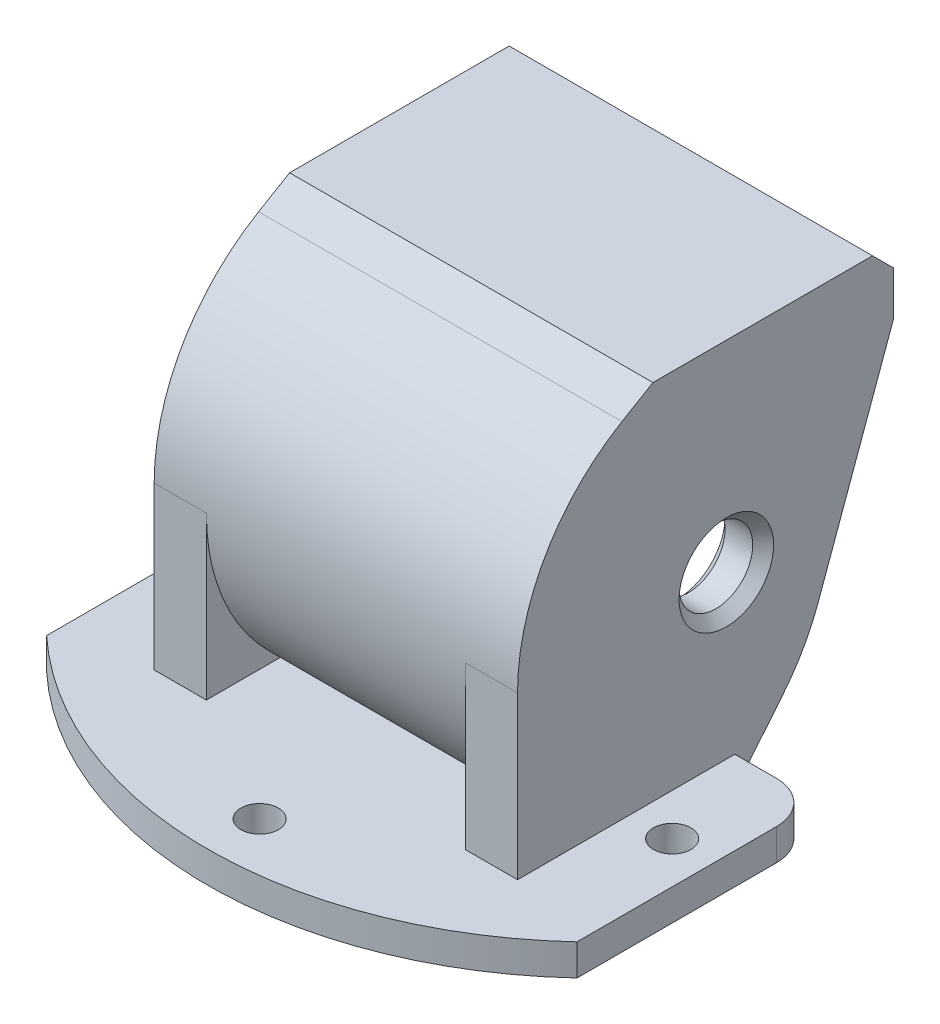
SolidWorks part; units mm, degrees
ref_plane "Front Plane" through (0, 0, 0) normal (0, 0, 1) x (1, 0, 0)
ref_plane "Top Plane" through (0, 0, 0) normal (0, 1, 0) x (1, 0, 0)
ref_plane "Right Plane" through (0, 0, 0) normal (1, 0, 0) x (0, 0, -1)
sketch "Sketch1" plane through (0, 0, 0) normal (1, 0, 0) x (0, 0, -1)
  line L0 (0, 17.5) -> (0, -17.5) construction
  line L1 (0, 17.5) -> (-10, 17.5)
  line L2 (10, 17.5) -> (10, -17.5) construction
  line L3 (0, -17.5) -> (-10, -17.5)
  line L4 (-10, 17.5) -> (-10, -17.5) construction
  line L5 (0, 0) -> (10, 0) construction
  line L6 (0, 0) -> (-10, 0) construction
  line L7 (0, 0) -> (-10, 0) construction
  line L8 (-10, 0) -> (-20, 0) construction
  arc A0 (0, -17.5) -> (0, 17.5) centre (-10.3125, 0) ccw
  arc A1 (-10, 17.5) -> (-10, -17.5) centre (0.3125, 0) ccw
  dimension "D3" = 20
  dimension "D1" = 35
extrude "Boss-Extrude1" add sketch "Sketch1" against normal mid plane 34.8
sketch "Sketch2" plane through (0, 0, 0) normal (1, 0, 0) x (0, 0, -1)
  line L0 (0, 17.5) -> (-10, 17.5) construction
  line L1 (-10, -17.5) -> (0, -17.5) construction
  line L2 (-16, 0) -> (-20, 0) construction
  line L4 (-10, -17.5) -> (0, -17.5)
  line L5 (0, 17.5) -> (-10, 17.5)
  line L6 (-6, -17.5) -> (0, -17.5)
  line L7 (0, 17.5) -> (-6, 17.5)
  arc A0 (-6, 17.5) -> (-6, -17.5) centre (4.3125, 0) ccw
  arc A1 (-10, 17.5) -> (-10, -17.5) centre (0.3125, 0) ccw construction
  arc A4 (-10, 17.5) -> (-10, -17.5) centre (0.3125, 0) ccw
  arc A5 (0, -17.5) -> (0, 17.5) centre (-10.3125, 0) ccw
  arc A7 (0, -17.5) -> (0, 17.5) centre (-10.3125, 0) ccw
  dimension "D1" = 0
  dimension "D2" = 4
extrude "Cut-Extrude1" cut sketch "Sketch2" along normal mid plane 25.5
sketch "Sketch3" plane through (0, 0, 0) normal (1, 0, 0) x (0, 0, -1)
  line L0 (-9.5, -17.5) -> (-9.5, -24)
  line L1 (-10, -17.5) -> (0, -17.5) construction
  line L2 (-0.5, -24) -> (-0.5, -17.5)
  line L3 (-0.5, -17.5) -> (-9.5, -17.5)
  line L4 (-5, -28.5) -> (-5, -17.5) construction
  arc A0 (-9.5, -24) -> (-0.5, -24) centre (-5, -24) ccw
  dimension "D1" = 9
  dimension "D2" = 6.5
extrude "Boss-Extrude2" add sketch "Sketch3" along normal mid plane 10
sketch "Sketch4" plane through (17.4, 0, 0) normal (1, 0, 0) x (0, 0, -1)
  line L0 (-13.4374, -9.8761) -> (0.9816, -18.201)
  line L1 (0.8089, -18.5) -> (-8.303, -18.5)
  line L4 (-13.4374, -9.8761) -> (-17.4374, -9.8761)
  line L5 (0.8089, -18.5) -> (0.9816, -18.201)
  line L8 (0, 0) -> (14.9634, 0.0217) construction
  line L9 (14.9634, 0.0217) -> (14.9855, -15.25) construction
  line L10 (69.9999, 0.1014) -> (0, 0) construction
  line L12 (-10, -17.5) -> (-8.303, -18.5)
  line L13 (0.9816, -18.201) -> (8.6174, -4.9753) construction
  line L14 (0, 0) -> (8.6174, -4.9753) construction
  line L15 (0, 0) -> (-8.348, 0) construction
  line L16 (-10, -17.5) -> (0, -17.5) construction
  arc A0 (-10, 17.5) -> (-10, -17.5) centre (0.3125, 0) ccw construction
  arc A2 (-6, 17.5) -> (-6, -17.5) centre (4.3125, 0) ccw construction
  arc A3 (-6, 17.5) -> (-6, -17.5) centre (4.3125, 0) ccw construction
  arc A4 (-17.4374, -9.8761) -> (-10, -17.5) centre (0.3125, 0) ccw
  dimension "D1" = 30
  dimension "D2" = 0.299
  dimension "D3" = 1
extrude "Boss-Extrude3" add sketch "Sketch4" against normal up to surface (34.8 mm away) up to face at (-17.4, 0, 5)
sketch "Sketch5" plane through (17.4, 0, 0) normal (1, 0, 0) x (0, 0, -1)
  line L4 (-8.303, -18.5) -> (0.8089, -18.5) construction
  line L5 (5.426, -12.8412) -> (0.8089, -18.5)
  line L6 (0.8089, -18.5) -> (0.9816, -18.201) construction
  line L7 (0.8089, -18.5) -> (-1.1911, -18.5)
  line L8 (-1.1911, -18.5) -> (-1.1911, -17.5)
  line L9 (-1.1911, -17.5) -> (5.426, -12.8412)
  arc A3 (0, -17.5) -> (0, 17.5) centre (-10.3125, 0) ccw construction
  dimension "D1" = 1
  dimension "D2" = 2
extrude "Boss-Extrude4" add sketch "Sketch5" against normal up to surface (4.65 mm away) up to face at (12.75, -1.6725, 3.0481)
sketch "Sketch6" plane through (-17.4, 0, 0) normal (-1, 0, 0) x (0, 0, 1)
  line L2 (-5.426, -12.8412) -> (-0.8089, -18.5)
  line L3 (-5.426, -12.8412) -> (-0.8089, -18.5)
  line L4 (-0.8089, -18.5) -> (1.1911, -18.5)
  line L5 (-0.8089, -18.5) -> (1.1911, -18.5)
  line L12 (1.1911, -18.5) -> (1.1911, -17.5)
  line L13 (1.1911, -18.5) -> (1.1911, -17.5)
  line L14 (1.1911, -17.5) -> (-5.426, -12.8412)
  line L15 (1.1911, -17.5) -> (-5.426, -12.8412)
  dimension "D1" = 0
extrude "Boss-Extrude5" add sketch "Sketch6" against normal up to surface (4.65 mm away) up to face at (-12.75, -1.6725, 3.0481)
sketch "Sketch7" plane through (17.4, 0, 0) normal (1, 0, 0) x (0, 0, -1)
  line L0 (-10, 17.5) -> (-7.0303, 19.25)
  line L1 (-7.0303, 19.25) -> (16, 19.25)
  line L2 (16, 19.25) -> (16, 12.9763)
  line L3 (0, 0) -> (2.3856, 15.0622) construction
  line L4 (3.1052, 15.25) -> (-13.1052, 15.25)
  line L6 (0, 0) -> (0, 15.25) construction
  line L7 (69.1382, -10.9504) -> (0, 0) construction
  line L8 (86.7145, 1.7059) -> (32.5901, 10.2783) construction
  line L9 (0, 17.5) -> (-10, 17.5) construction
  line L10 (3.1052, 15.25) -> (16, 12.9763)
  line L11 (0, 17.5) -> (-10, 17.5) construction
  line L13 (10, 0) -> (10, 11.0966) construction
  line L14 (0, 0) -> (69.1382, 0) construction
  arc A0 (-10, 17.5) -> (-10, -17.5) centre (0.3125, 0) ccw construction
  arc A1 (-10, 17.5) -> (-13.1052, 15.25) centre (0.3125, 0) ccw
  arc A3 (5.426, -12.8412) -> (0, 17.5) centre (-10.3125, 0) ccw construction
  dimension "D1" = 10
  dimension "D2" = 4
  dimension "D3" = 6
extrude "Boss-Extrude6" add sketch "Sketch7" against normal up to surface (34.8 mm away) up to face at (-17.4, -5.1825, 4.1831)
sketch "Sketch8" plane through (17.4, 0, 0) normal (1, 0, 0) x (0, 0, -1)
  line L0 (16, 12.9763) -> (8.7832, -6.9248)
  line L2 (3.1052, 15.25) -> (16, 12.9763)
  arc A0 (5.426, -12.8412) -> (3.1052, 15.25) centre (-10.3125, 0) ccw construction
  arc A1 (8.7832, -6.9248) -> (3.1052, 15.25) centre (-10.3125, 0) ccw
extrude "Boss-Extrude7" add sketch "Sketch8" against normal up to surface (4.65 mm away) up to face at (12.75, -4.6143, 1.8315)
sketch "Sketch9" plane through (-17.4, 0, 0) normal (-1, 0, 0) x (0, 0, 1)
  line L2 (-16, 12.9763) -> (-8.7832, -6.9248)
  line L3 (-3.1052, 15.25) -> (-16, 12.9763)
  line L4 (-16, 12.9763) -> (-8.7832, -6.9248)
  line L5 (-3.1052, 15.25) -> (-16, 12.9763)
  arc A1 (-3.1052, 15.25) -> (-8.7832, -6.9248) centre (10.3125, 0) ccw
  arc A2 (-3.1052, 15.25) -> (-8.7832, -6.9248) centre (10.3125, 0) ccw
  dimension "D1" = 0
extrude "Boss-Extrude8" add sketch "Sketch9" against normal up to surface (4.65 mm away) up to face at (-12.75, -4.6143, 1.8315)
chamfer "Chamfer2" distance 2 angle 45 1 edges at (0, 19.25, -16)
sketch "Sketch10" plane through (17.4, 0, 0) normal (1, 0, 0) x (0, 0, -1)
  circle A0 centre (0, 0) radius 3.175 construction
  circle A1 centre (0, 0) radius 3.525
  dimension "D1" = 6.35
  dimension "D2" = 0.35
extrude "Cut-Extrude2" cut sketch "Sketch10" against normal through all
sketch "Sketch11" plane through (0, 0, 0) normal (1, 0, 0) x (0, 0, -1)
  line L3 (-9.5, -17.5) -> (-9.5, -24)
  line L4 (-0.5, -24) -> (-0.5, -17.5)
  line L5 (-0.5, -17.5) -> (-9.5, -17.5)
  line L6 (-9.5, -17.5) -> (-9.5, -24)
  line L7 (-0.5, -24) -> (-0.5, -17.5)
  line L8 (-0.5, -17.5) -> (-9.5, -17.5)
  arc A1 (-9.5, -24) -> (-0.5, -24) centre (-5, -24) ccw
  arc A2 (-9.5, -24) -> (-0.5, -24) centre (-5, -24) ccw
  dimension "D1" = 0
extrude "Cut-Extrude3" cut sketch "Sketch11" against normal mid plane 0.762
chamfer "Chamfer3" [suppressed] distance 5 angle 45
sketch "Sketch12" plane through (0, -18.5, 0) normal (0, -1, 0) x (1, 0, 0)
  line L0 (-17.4, -0.8089) -> (-21.4, -0.8089)
  line L2 (21.4, -0.8089) -> (17.4, -0.8089)
  line L4 (-25.4, 22.303) -> (25.4, 22.303) construction
  line L8 (-25.4, 3.1911) -> (-25.4, 22.303)
  line L9 (25.4, 22.303) -> (25.4, 3.1911)
  line L10 (-17.4, 8.303) -> (-25.4, 8.303) construction
  line L11 (0, 22.303) -> (0, 32.303) construction
  line L12 (-17.4, -0.8089) -> (-17.4, 8.303) construction
  line L13 (17.4, 8.303) -> (25.4, 8.303) construction
  line L14 (17.4, 8.303) -> (17.4, -0.8089) construction
  line L15 (-17.4, -0.8089) -> (-17.4, 8.303)
  line L16 (17.4, 8.303) -> (17.4, -0.8089)
  line L17 (17.4, 8.303) -> (-17.4, 8.303)
  arc A0 (-21.4, -0.8089) -> (-25.4, 3.1911) centre (-21.4, 3.1911) cw
  arc A1 (25.4, 3.1911) -> (21.4, -0.8089) centre (21.4, 3.1911) cw
  arc A2 (-25.4, 22.303) -> (25.4, 22.303) centre (0, -4.955) cw
  dimension "D2" = 4
  dimension "D1" = 8
  dimension "D3" = 10
  dimension "D4" = 14
extrude "Boss-Extrude9" add sketch "Sketch12" against normal blind 3
sketch "Sketch13" plane through (-17.4, 0, 0) normal (-1, 0, 0) x (0, 0, 1)
  line L0 (20, -15.5) -> (12.8156, -15.5) construction
  line L1 (20, -15.5) -> (20, 0)
  line L3 (12.8156, -15.5) -> (12.8156, -23.5)
  line L4 (12.8156, -23.5) -> (20, -23.5)
  line L5 (20, -23.5) -> (20, -15.5)
  line L6 (22.303, -18.5) -> (3.1911, -18.5) construction
  arc A0 (20, 0) -> (12.8156, -15.5) centre (-0.3125, 0) cw
  arc A1 (12.8156, -15.5) -> (10, 17.5) centre (-0.3125, 0) ccw construction
  dimension "D1" = 5
extrude "Boss-Extrude10" add sketch "Sketch13" against normal blind 5
mirror "Mirror1" about plane through (0, 0, 0) normal (1, 0, 0) of "Boss-Extrude10"
hole_wizard "M3 Clearance Hole1" positions "Sketch14" profile "Sketch15" hole size "M3" standard "ANSI Metric" end condition through all
sketch "Sketch14" plane through (0, -15.5, 0) normal (0, 1, 0) x (1, 0, 0)
  line L3 (0, -27.303) -> (0, -32.303) construction
  line L4 (-21.4, 0.8089) -> (-21.4, -9.1911) construction
  line L6 (21.4, 0.8089) -> (21.4, -9.1911) construction
  arc A1 (-25.4, -22.303) -> (25.4, -22.303) centre (0, 4.955) ccw construction
  point P10 (0, -27.303)
  point P34 (-21.4, -9.1911)
  point P36 (21.4, -9.1911)
  dimension "D1" = 5
  dimension "D2" = 10
sketch "Sketch15" plane through (0, -15.5, 27.303) normal (1, 0, 0) x (0, 0, 1)
  line L0 (0, 0) -> (0, 13)
  line L1 (0, 13) -> (1.8, 13)
  line L2 (1.8, 13) -> (1.8, 0)
  line L5 (1.8, 0) -> (0, 0)
  line L11 (0, -6.35) -> (0, 107.95) construction
  dimension "Thru Hole Dia." = 3.6
  dimension "Thru Hole Depth" = 13
hole_wizard "M3 Clearance Hole2" positions "Sketch16" profile "Sketch17" hole size "M3" standard "ANSI Metric" end condition through all
sketch "Sketch16" plane through (5, 0, 0) normal (1, 0, 0) x (0, 0, -1)
  point P0 (-5, -24)
sketch "Sketch17" plane through (5, -24, 5) normal (0, 1, 0) x (0, 0, -1)
  line L0 (0, 0) -> (0, 30.4)
  line L1 (0, 30.4) -> (1.8, 30.4)
  line L2 (1.8, 30.4) -> (1.8, 0)
  line L5 (1.8, 0) -> (0, 0)
  line L11 (0, -6.35) -> (0, 107.95) construction
  dimension "Thru Hole Dia." = 3.6
  dimension "Thru Hole Depth" = 30.4
chamfer "Chamfer5" distance 1 angle 45 4 edges at (17.4, 0, -3.525) (-12.75, 0, -3.525) (-17.4, 0, -3.525) (12.75, 0, -3.525)
sketch "Sketch18" plane through (0, 0, 0) normal (1, 0, 0) x (0, 0, -1)
  line L0 (0.9816, -18.201) -> (-13.4374, -9.8761)
  line L1 (-0.2321, -17.5002) -> (-13.4374, -9.8761) construction
  line L2 (-11.421, -18.5) -> (-0.5, -18.5) construction
  line L3 (-3.1911, -18.5) -> (-22.303, -18.5) construction
  line L4 (-0.5, -18.5) -> (1.4995, -18.5)
  line L5 (1.4995, -18.5) -> (-0.2321, -17.5002)
  arc A0 (-0.2321, -17.5002) -> (-0.5, -18.5) centre (-0.5, -17.9642) cw
extrude "Cut-Extrude4" cut sketch "Sketch18" against normal up to surface and the other way up to surface up to face at (-12.75, 0, -4.525) other way up to face at (12.75, 0, -4.525)
chamfer "Chamfer6" distance 1 angle 45 8 edges at (-14.9, -23.5, 20) (-12.4, -23.5, 16.4078) (-14.9, -23.5, 12.8156) (-17.4, -23.5, 16.4078) (14.9, -23.5, 12.8156) (12.4, -23.5, 16.4078) (14.9, -23.5, 20) (17.4, -23.5, 16.4078)
